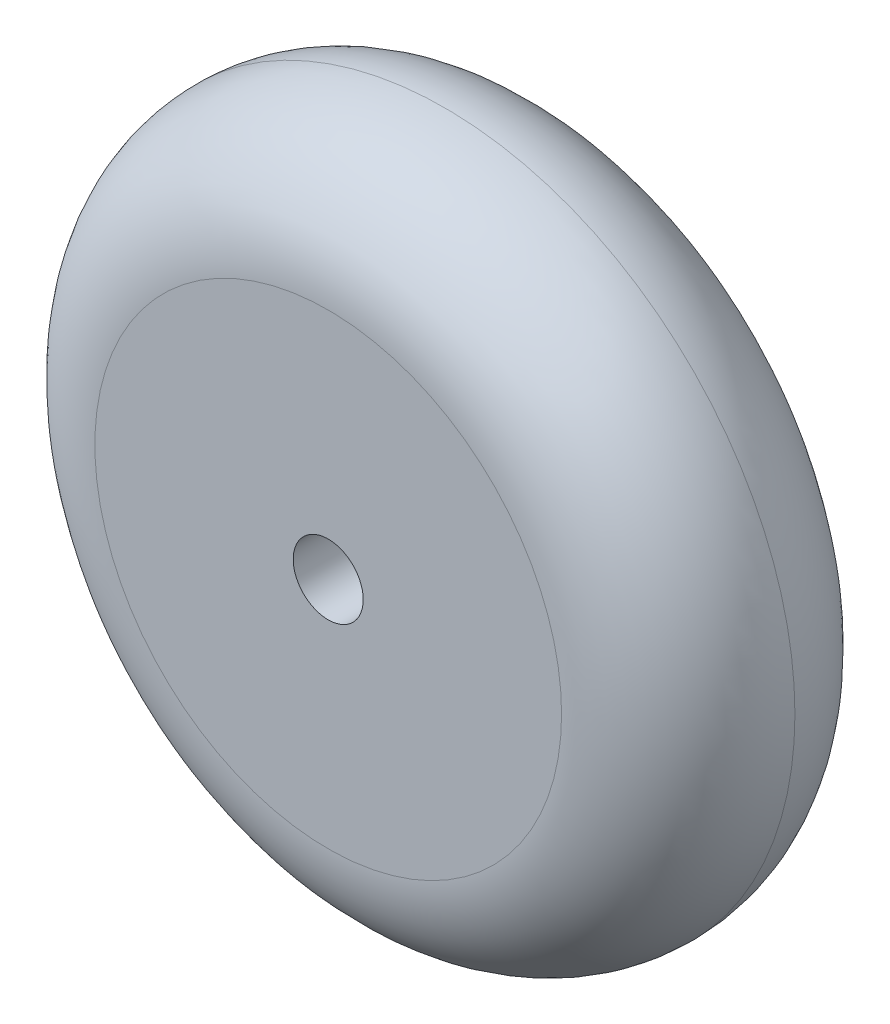
SolidWorks part; units mm, degrees
material "POLYURETHANE (11671)"
ref_plane "Front Plane" through (0, 0, 0) normal (0, 0, 1) x (1, 0, 0)
ref_plane "Top Plane" through (0, 0, 0) normal (0, 1, 0) x (1, 0, 0)
ref_plane "Right Plane" through (0, 0, 0) normal (1, 0, 0) x (0, 0, -1)
sketch "Sketch1" plane through (0, 0, 0) normal (0, 0, 1) x (1, 0, 0)
  circle A0 centre (0, 0) radius 15
  dimension "D1" = 30
extrude "Boss-Extrude1" add sketch "Sketch1" along normal blind 10
fillet "Fillet1" radius 5 1 edges at (15, 0, 10)
fillet "Fillet2" radius 5 1 edges at (15, 0, 0)
sketch "Sketch2" plane through (0, 0, 10) normal (0, 0, 1) x (1, 0, 0)
  circle A0 centre (0, 0) radius 1.5
  dimension "D1" = 3
extrude "Cut-Extrude1" cut sketch "Sketch2" against normal through all
